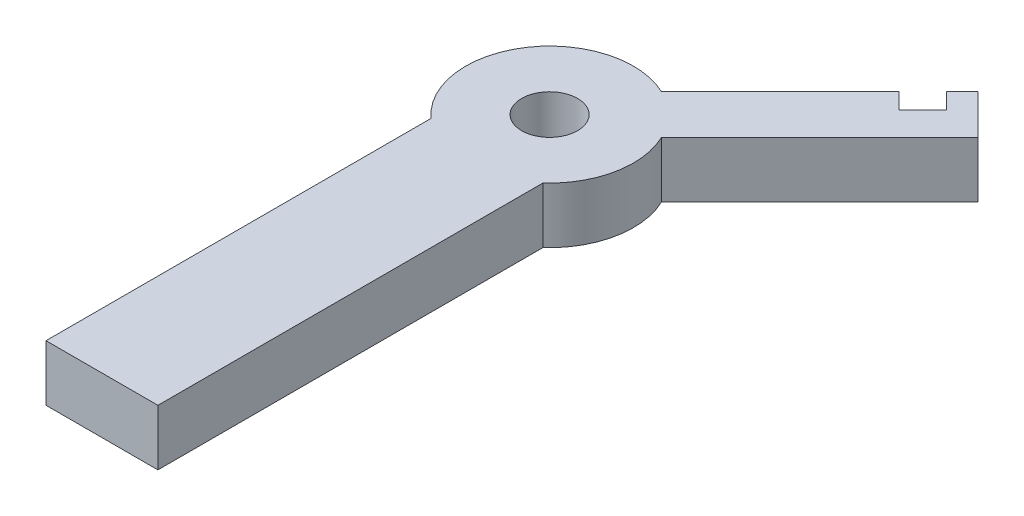
SolidWorks part; units mm, degrees
ref_plane "Front Plane" through (0, 0, 0) normal (0, 0, 1) x (1, 0, 0)
ref_plane "Top Plane" through (0, 0, 0) normal (0, 1, 0) x (1, 0, 0)
ref_plane "Right Plane" through (0, 0, 0) normal (1, 0, 0) x (0, 0, -1)
sketch "Sketch1" plane through (0, 0, 0) normal (0, 1, 0) x (1, 0, 0)
  line L0 (4.1049, 8.5951) -> (17.5753, 22.0654)
  line L1 (3.175, 0) -> (-3.175, 0)
  line L2 (6.35, -7.0995) -> (6.35, -50.8)
  line L3 (6.35, -50.8) -> (-6.35, -50.8)
  line L4 (-6.35, -7.0995) -> (-6.35, -50.8)
  line L5 (22.0654, 26.5556) -> (26.5556, 22.0654)
  line L6 (26.5556, 22.0654) -> (8.5951, 4.1049)
  line L7 (24.3105, 24.3105) -> (0, 0) construction
  line L8 (20.2694, 24.7595) -> (22.0654, 22.9635)
  line L9 (22.0654, 22.9635) -> (19.3714, 20.2694)
  line L10 (19.3714, 20.2694) -> (17.5753, 22.0654)
  line L11 (20.2694, 24.7595) -> (22.0654, 26.5556)
  circle A0 centre (0, 0) radius 3.175
  arc A1 (4.1049, 8.5951) -> (-6.35, -7.0995) centre (0, 0) ccw
  arc A2 (6.35, -7.0995) -> (8.5951, 4.1049) centre (0, 0) ccw
  dimension "D1" = 6.35
  dimension "D2" = 19.05
  dimension "D3" = 12.7
  dimension "D4" = 6.35
  dimension "D5" = 25.4
  dimension "D6" = 45
  dimension "D7" = 6.35
  dimension "D8" = 135
  dimension "D9" = 3.81
  dimension "D10" = 2.54
  dimension "D11" = 2.54
extrude "Boss-Extrude1" add sketch "Sketch1" along normal mid plane 6.35 contours L2 A2 L6 L5 A0 L11 L8 L9 L10 L0 A1 L4 L3 region at (2.4193, 0, 14.5823)
